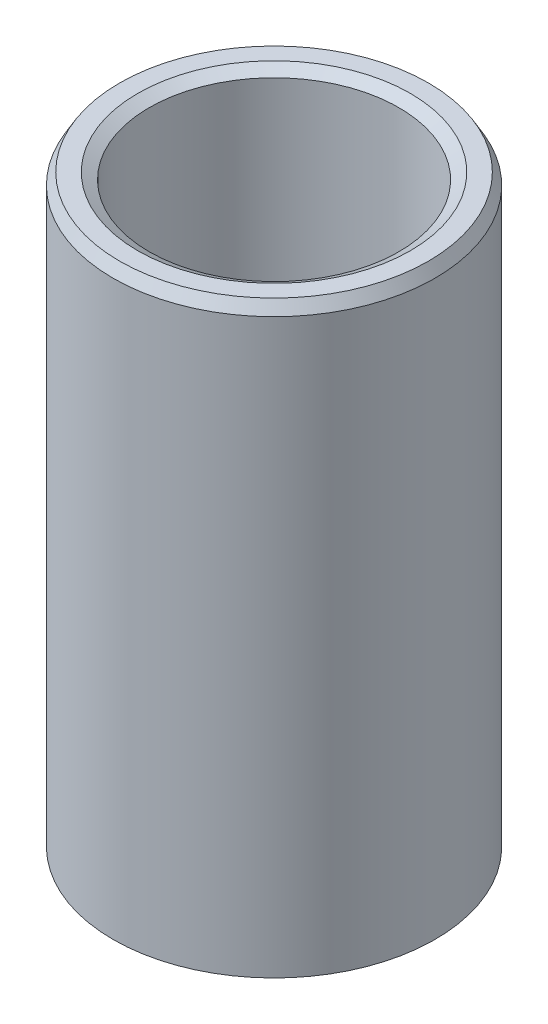
SolidWorks part; units mm, degrees
ref_plane "Front Plane" through (0, 0, 0) normal (0, 0, 1) x (1, 0, 0)
ref_plane "Top Plane" through (0, 0, 0) normal (0, 1, 0) x (1, 0, 0)
ref_plane "Right Plane" through (0, 0, 0) normal (1, 0, 0) x (0, 0, -1)
sketch "Sketch1" plane through (0, 0, 0) normal (0, 1, 0) x (1, 0, 0)
  circle A0 centre (0, 0) radius 40
  dimension "SLEEVE_OD" = 80
extrude "Boss-Extrude1" add sketch "Sketch1" along normal blind 146.7795
sketch "Sketch2" plane through (0, 0, 0) normal (0, 1, 0) x (1, 0, 0)
  circle A0 centre (0, 0) radius 31.0208
  dimension "BORE_D" = 62.0416
extrude "Cut-Extrude1" cut sketch "Sketch2" along normal through all
chamfer "Chamfer1" distance 2.8452 angle 30 4 edges at (0, 146.7795, 31.0208) (0, 0, 31.0208) (0, 0, 40) (0, 146.7795, 40) first distance on face at (0, 146.7795, 31.0208) first distance on face at (0, 0, 31.0208) first distance on face at (0, 146.7795, 40)
